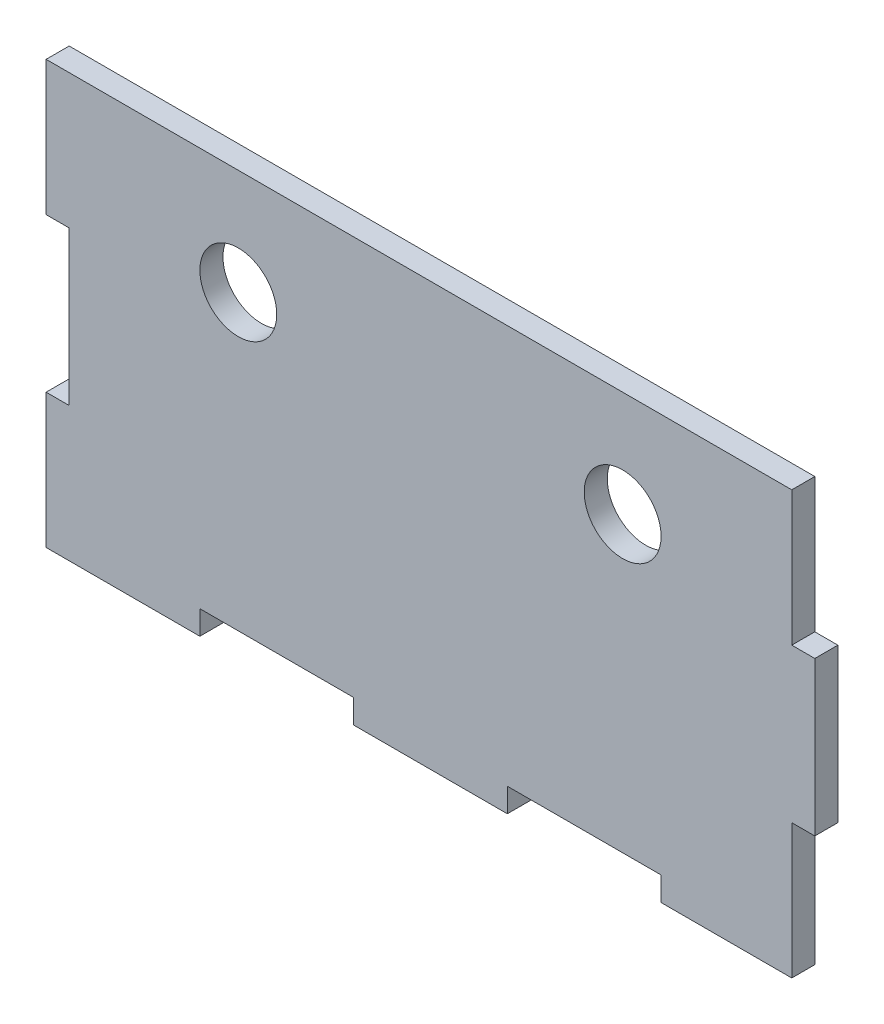
SolidWorks part; units mm, degrees
ref_plane "Front Plane" through (0, 0, 0) normal (0, 0, 1) x (1, 0, 0)
ref_plane "Top Plane" through (0, 0, 0) normal (0, 1, 0) x (1, 0, 0)
ref_plane "Right Plane" through (0, 0, 0) normal (1, 0, 0) x (0, 0, -1)
sketch "Sketch1" plane through (0, 0, 0) normal (0, 0, 1) x (1, 0, 0)
  line L0 (-50, -27.5) -> (-50, -10)
  line L1 (-50, -27.5) -> (50, -27.5)
  line L2 (-50, -27.5) -> (-50, 27.5)
  line L3 (-50, 27.5) -> (50, 27.5)
  line L4 (50, -27.5) -> (50, 27.5)
  line L5 (-50, -27.5) -> (50, 27.5) construction
  line L6 (-50, 27.5) -> (50, -27.5) construction
  line L7 (-50, -10) -> (-47, -10)
  line L8 (-47, -10) -> (-47, 10)
  line L9 (-47, 10) -> (-50, 10)
  line L10 (-50, 10) -> (-50, 27.5)
  line L11 (50, -10) -> (47, -10)
  line L12 (47, -10) -> (47, -27.5)
  line L13 (50, 10) -> (47, 10)
  line L14 (47, 10) -> (47, 27.5)
  line L15 (-50, -27.5) -> (-30, -27.5)
  line L16 (-30, -27.5) -> (-30, -24.3935)
  line L17 (-30, -24.3935) -> (-10, -24.3935)
  line L18 (-10, -24.3935) -> (-10, -27.5)
  line L19 (-10, -27.5) -> (10, -27.5)
  line L20 (10, -27.5) -> (10, -24.3935)
  line L21 (10, -24.3935) -> (30, -24.3935)
  line L22 (30, -24.3935) -> (30, -27.5)
  circle A0 centre (-25, 13.75) radius 5
  circle A1 centre (25, 13.75) radius 5
  point P0 (0, 0)
  dimension "D12" = 10
  dimension "D15" = 10
  dimension "D1" = 55
  dimension "D2" = 17.5
  dimension "D3" = 17.5
  dimension "D4" = 3
  dimension "D5" = 3
  dimension "D6" = 3
  dimension "D7" = 100
  dimension "D8" = 20
  dimension "D9" = 20
  dimension "D10" = 20
  dimension "D11" = 20
  dimension "D13" = 25
  dimension "D14" = 13.75
extrude "Boss-Extrude1" add sketch "Sketch1" along normal blind 3 contours L13 L14 L3 L2 L9 L8 L7 L0 L1 L12 L11 L4 region at (-0.4319, 0.2106, 0)
